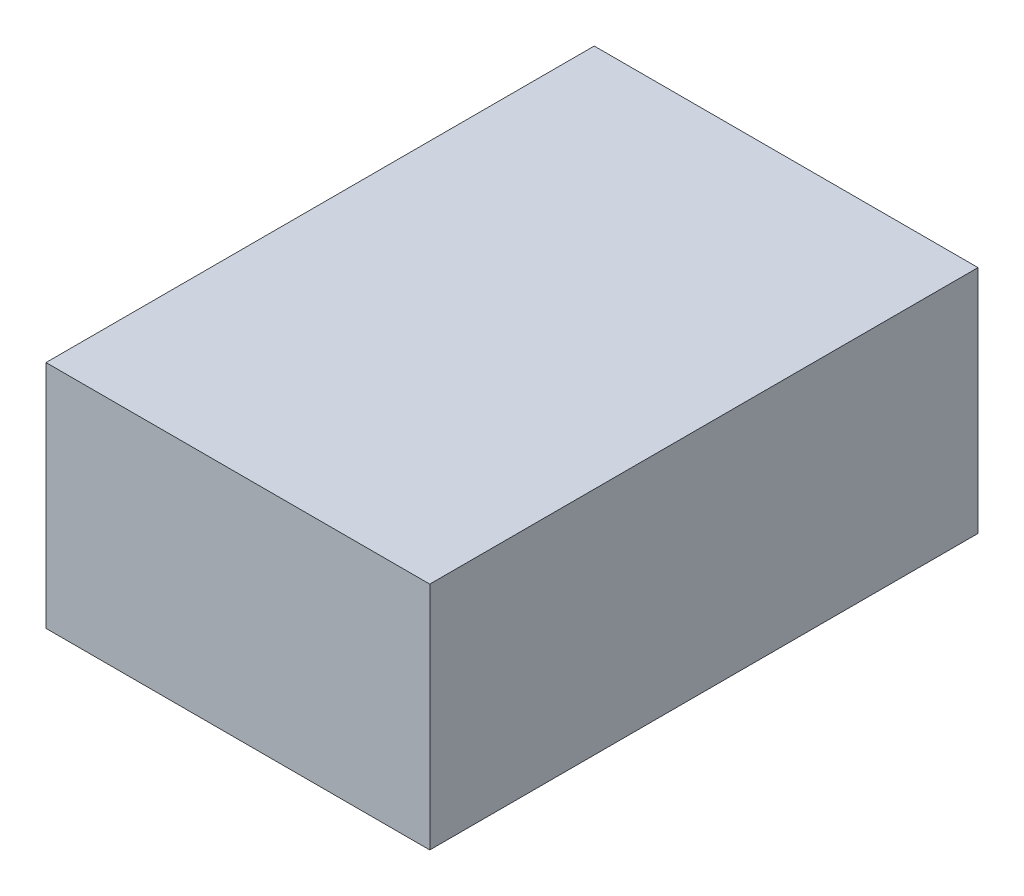
SolidWorks part; units mm, degrees
ref_plane "Front Plane" through (0, 0, 0) normal (0, 0, 1) x (1, 0, 0)
ref_plane "Top Plane" through (0, 0, 0) normal (0, 1, 0) x (1, 0, 0)
ref_plane "Right Plane" through (0, 0, 0) normal (1, 0, 0) x (0, 0, -1)
sketch "Sketch1" plane through (0, 0, 0) normal (0, 0, 1) x (1, 0, 0)
  line L1 (-4.6054, 5.2352) -> (4.2846, 5.2352)
  line L2 (-4.6054, 5.2352) -> (-4.6054, -0.0988)
  line L3 (-4.6054, -0.0988) -> (4.2846, -0.0988)
  line L4 (4.2846, 5.2352) -> (4.2846, -0.0988)
  dimension "D1" = 8.89
  dimension "D2" = 5.334
extrude "Boss-Extrude1" add sketch "Sketch1" along normal blind 12.7
